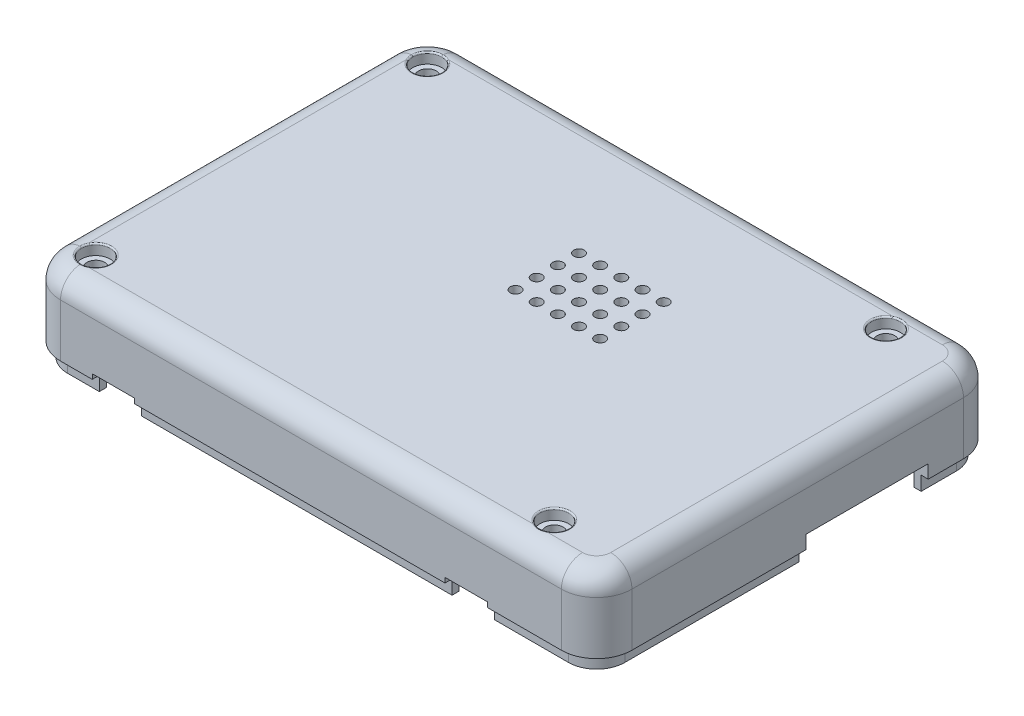
SolidWorks part; units mm, degrees
ref_plane "前视基准面" through (0, 0, 0) normal (0, 0, 1) x (1, 0, 0)
ref_plane "上视基准面" through (0, 0, 0) normal (0, 1, 0) x (1, 0, 0)
ref_plane "右视基准面" through (0, 0, 0) normal (1, 0, 0) x (0, 0, -1)
sketch "草图4" plane through (0, 0, 0) normal (0, 1, 0) x (1, 0, 0)
  line L1 (-118.546, 139.5567) -> (-41.546, 139.5567)
  line L2 (-118.546, 139.5567) -> (-118.546, 86.5567)
  line L3 (-118.546, 86.5567) -> (-41.546, 86.5567)
  line L4 (-41.546, 139.5567) -> (-41.546, 86.5567)
  line L5 (-39.546, 141.5567) -> (-39.546, 84.5567)
  line L6 (-120.546, 84.5567) -> (-39.546, 84.5567)
  line L7 (-120.546, 141.5567) -> (-120.546, 84.5567)
  line L8 (-120.546, 141.5567) -> (-39.546, 141.5567)
  circle A0 centre (-115.546, 136.5567) radius 1.25
  circle A1 centre (-50.546, 136.5567) radius 1.25
  circle A2 centre (-50.546, 89.5567) radius 1.25
  circle A3 centre (-115.546, 89.5567) radius 1.25
  circle A4 centre (-115.546, 136.5567) radius 2.5
  circle A5 centre (-50.546, 136.5567) radius 2.5
  circle A6 centre (-50.546, 89.5567) radius 2.5
  circle A7 centre (-115.546, 89.5567) radius 2.5
  dimension "D3" = 5
  dimension "D4" = 5
  dimension "D5" = 5
  dimension "D6" = 5
  dimension "D7" = 2.5
  dimension "D9" = 3
  dimension "D1" = 77
  dimension "D2" = 53
  dimension "D8" = 3
  dimension "D10" = 2
extrude "凸台-拉伸5" add sketch "草图4" against normal blind 3 contours A0 | A1 | A2 | A3 | L5 L6 L7 L8 region at (-115.546, 0, -136.5567) region at (-50.546, 0, -136.5567) region at (-50.546, 0, -89.5567) region at (-115.546, 0, -89.5567)
extrude "凸台-拉伸6" add sketch "草图4<4>" against normal blind 10.6 from surface contours A6 A2 | A7 A3 | A5 A1 | A4 A0 region at (-117.9753, 0, -136.5567) region at (-52.9753, 0, -136.5567) region at (-52.9753, 0, -89.5567) region at (-117.9753, 0, -89.5567) starting at face at (-115.546, -3, -88.3067)
sketch "草图4<4>" plane through (0, 0, 0) normal (0, 1, 0) x (1, 0, 0) same geometry as "草图4"
extrude "凸台-拉伸7" add sketch "草图4<5>" against normal blind 10.5 contours L8 L7 L6 L5 L1 L4 L3 L2 region at (-40.5364, 0, -113.0567)
sketch "草图4<5>" plane through (0, 0, 0) normal (0, 1, 0) x (1, 0, 0) same geometry as "草图4"
sketch "草图6" plane through (0, 0, -141.5567) normal (0, 0, -1) x (-1, 0, 0)
  line L0 (120.546, -10.5) -> (39.546, -10.5) construction
  line L1 (59.546, -10.5) -> (72.046, -10.5)
  line L2 (59.546, -8.35) -> (59.546, -12.65)
  line L3 (59.546, -12.65) -> (72.046, -12.65)
  line L4 (72.046, -8.35) -> (72.046, -12.65)
  line L5 (120.546, -10.5) -> (39.546, -10.5) construction
  line L6 (75.446, -10.5) -> (85.446, -10.5)
  line L7 (75.446, -8.35) -> (75.446, -12.65)
  line L8 (75.446, -12.65) -> (85.446, -12.65)
  line L9 (85.446, -8.35) -> (85.446, -12.65)
  line L10 (89.446, -10.5) -> (96.946, -10.5)
  line L11 (89.446, -7.35) -> (89.446, -13.65)
  line L12 (89.446, -13.65) -> (96.946, -13.65)
  line L13 (96.946, -7.35) -> (96.946, -13.65)
  line L14 (103.946, -10.5) -> (112.946, -10.5)
  line L15 (103.946, -10) -> (103.946, -10.5)
  line L16 (112.946, -10) -> (112.946, -10.5)
  line L18 (103.946, -10) -> (112.946, -10)
  line L19 (89.446, -7.35) -> (96.946, -7.35)
  line L20 (75.446, -8.35) -> (85.446, -8.35)
  line L21 (59.546, -8.35) -> (72.046, -8.35)
  line L23 (39.546, -10.5) -> (39.546, 0) construction
  line M25 (39.546, -10.5) -> (120.546, -10.5)
  dimension "D1" = 12.5
  dimension "D2" = 20
  dimension "D3" = 3.4
  dimension "D4" = 10
  dimension "D5" = 4
  dimension "D6" = 7.5
  dimension "D7" = 3.15
  dimension "D8" = 7
  dimension "D9" = 0.5
extrude "切除-拉伸1" cut sketch "草图6" against normal blind 2 contours L21 L2 L4 M25 | L20 L7 L9 M25 | L19 L11 L13 M25 | L18 L16 L14 L15 region at (-65.796, -9.425, -141.5567) region at (-93.196, -8.925, -141.5567) region at (-80.446, -9.425, -141.5567)
sketch "草图7" plane through (-120.546, 0, 0) normal (-1, 0, 0) x (0, 0, 1)
  line L1 (-133.2567, -10.5) -> (-133.2567, -3)
  line L2 (-133.2567, -3) -> (-124.3067, -3)
  line L3 (-124.3067, -3) -> (-124.3067, -10.5)
  line L4 (-141.5567, -10.5) -> (-141.5567, 0) construction
  line L6 (-84.5567, -10.5) -> (-84.5567, 0) construction
  line L11 (-106.4567, -9.3) -> (-95.5567, -9.3)
  line L12 (-106.4567, -9.3) -> (-106.4567, -10.5)
  line L13 (-141.5567, -10.5) -> (-84.5567, -10.5) construction
  line L18 (-95.5567, -9.3) -> (-95.5567, -10.5)
  line M23 (-141.5567, -10.5) -> (-84.5567, -10.5)
  dimension "D1" = 11
  dimension "D2" = 8.3
  dimension "D3" = 8.95
  dimension "D4" = 1.2
  dimension "D5" = 7.5
  dimension "D6" = 10.9
extrude "切除-拉伸2" cut sketch "草图7" against normal blind 2 contours L18 L11 L12 M23 | L3 L2 L1 M23 region at (-120.546, -9.9, -101.0067) region at (-120.546, -6.75, -128.7817)
sketch "草图8" plane through (0, 0, -84.5567) normal (0, 0, 1) x (1, 0, 0)
  line L0 (-120.546, -10.5) -> (-39.546, -10.5) construction
  line L1 (-111.046, -10.5) -> (-105.046, -10.5)
  line L2 (-111.046, -9.8) -> (-111.046, -11.2)
  line L3 (-111.046, -11.2) -> (-105.046, -11.2)
  line L4 (-105.046, -9.8) -> (-105.046, -11.2)
  line L5 (-39.546, -10.5) -> (-39.546, 0) construction
  line L6 (-61.046, -10.5) -> (-55.046, -10.5)
  line L7 (-61.046, -9.8) -> (-61.046, -11.2)
  line L8 (-61.046, -11.2) -> (-55.046, -11.2)
  line L9 (-55.046, -9.8) -> (-55.046, -11.2)
  line L10 (-120.546, -10.5) -> (-120.546, 0) construction
  line L11 (-120.546, -10.5) -> (-39.546, -10.5) construction
  line L12 (-61.046, -9.8) -> (-55.046, -9.8)
  line L13 (-111.046, -9.8) -> (-105.046, -9.8)
  line M18 (-120.546, -10.5) -> (-39.546, -10.5)
  dimension "D1" = 6
  dimension "D2" = 6
  dimension "D3" = 15.5
  dimension "D4" = 9.5
  dimension "D5" = 0.7
extrude "切除-拉伸3" cut sketch "草图8" against normal blind 2 contours L13 L2 L4 M18 | L12 L7 L9 M18 region at (-108.046, -10.15, -84.5567) region at (-58.046, -10.15, -84.5567)
sketch "草图9" plane through (-39.546, 0, 0) normal (1, 0, 0) x (0, 0, -1)
  line L0 (141.5567, -10.5) -> (84.5567, -10.5) construction
  line L1 (114.2567, -10.5) -> (131.5567, -10.5)
  line L2 (114.2567, -8.6) -> (114.2567, -12.4)
  line L3 (114.2567, -12.4) -> (131.5567, -12.4)
  line L4 (131.5567, -8.6) -> (131.5567, -12.4)
  line L5 (141.5567, -10.5) -> (141.5567, 0) construction
  line L6 (141.5567, -10.5) -> (84.5567, -10.5) construction
  line L7 (114.2567, -8.6) -> (131.5567, -8.6)
  line M12 (84.5567, -10.5) -> (141.5567, -10.5)
  dimension "D1" = 10
  dimension "D2" = 17.3
  dimension "D3" = 1.9
extrude "切除-拉伸4" cut sketch "草图9" against normal blind 2 contours L7 L2 L4 M12 region at (-39.546, -9.55, -122.9067)
fillet "圆角2" radius 3 4 edges at (-41.546, -6.75, -86.5567) (-41.546, -6.75, -139.5567) (-118.546, -6.75, -139.5567) (-118.546, -6.75, -86.5567)
fillet "圆角3" radius 5 4 edges at (-120.546, -5.25, -84.5567) (-39.546, -5.25, -84.5567) (-39.546, -5.25, -141.5567) (-120.546, -5.25, -141.5567)
fillet "圆角4" radius 3 8 edges at (-119.0815, 0, -86.0211) (-120.546, 0, -113.0567) (-119.0815, 0, -140.0922) (-80.046, 0, -141.5567) (-41.0104, 0, -140.0922) (-39.546, 0, -113.0567) (-41.0104, 0, -86.0211) (-80.046, 0, -84.5567)
fillet "圆角5" radius 2 2 edges at (-119.546, -9.3, -95.5567) (-119.546, -9.3, -106.4567)
fillet "圆角6" radius 3.5 2 edges at (-119.546, -3, -124.3067) (-119.546, -3, -133.2567)
sketch "草图10" plane through (0, 0, 0) normal (0, 1, 0) x (1, 0, 0)
  circle A0 centre (-50.546, 89.5567) radius 2.05
  circle A1 centre (-115.546, 89.5567) radius 2.05
  circle A2 centre (-115.546, 136.5567) radius 2.05
  circle A3 centre (-50.546, 136.5567) radius 2.05
  dimension "D1" = 4.1
extrude "切除-拉伸5" cut sketch "草图10" against normal blind 1.5
fillet "圆角7" radius 0.2 12 edges at (-116.9955, -0.0004, -88.1071) (-114.0964, 0, -135.1071) (-50.7834, -0.0002, -138.5929) (-50.3086, -0.0002, -87.5205) (-114.0964, 0, -91.0062) (-116.9955, -0.0004, -138.0062) (-50.546, 0, -134.5067) (-50.546, 0, -91.6067)
sketch "草图12" plane through (0, -10.5, 0) normal (0, -1, 0) x (1, 0, 0)
  line L0 (-59.546, -141.5567) -> (-44.546, -141.5567) construction
  line L1 (-44.546, -85.5567) -> (-115.546, -85.5567)
  line L2 (-40.546, -89.5567) -> (-40.546, -136.5567)
  line L3 (-44.546, -140.5567) -> (-115.546, -140.5567)
  line L4 (-119.546, -89.5567) -> (-119.546, -136.5567)
  line L5 (-39.546, -114.2567) -> (-39.546, -131.5567) construction
  line L6 (-105.046, -84.5567) -> (-61.046, -84.5567) construction
  line L7 (-120.546, -124.3067) -> (-120.546, -106.4567) construction
  line L8 (-44.546, -86.5567) -> (-115.546, -86.5567)
  line L9 (-118.546, -89.5567) -> (-118.546, -136.5567)
  line L10 (-44.546, -139.5567) -> (-115.546, -139.5567)
  line L11 (-41.546, -89.5567) -> (-41.546, -136.5567)
  line L12 (-55.046, -84.5567) -> (-55.046, -86.5567)
  line L13 (-55.046, -86.5567) -> (-55.046, -84.5567) construction
  line L14 (-61.046, -84.5567) -> (-61.046, -86.5567)
  line L15 (-61.046, -86.5567) -> (-61.046, -84.5567) construction
  line L16 (-40.546, -114.2567) -> (-41.546, -114.2567)
  line L17 (-41.546, -114.2567) -> (-39.546, -114.2567) construction
  line L18 (-41.546, -131.5567) -> (-40.546, -131.5567)
  line L19 (-59.546, -139.5567) -> (-59.546, -140.5567)
  line L20 (-59.546, -139.5567) -> (-59.546, -141.5567) construction
  line L21 (-72.046, -140.5567) -> (-72.046, -139.5567)
  line L22 (-72.046, -139.5567) -> (-72.046, -141.5567) construction
  line L23 (-75.446, -139.5567) -> (-75.446, -140.5567)
  line L24 (-75.446, -139.5567) -> (-75.446, -141.5567) construction
  line L25 (-96.946, -139.5567) -> (-96.946, -140.5567)
  line L26 (-96.946, -139.5567) -> (-96.946, -141.5567) construction
  line L27 (-103.946, -139.5567) -> (-103.946, -140.5567)
  line L28 (-103.946, -139.5567) -> (-103.946, -141.5567) construction
  line L29 (-112.946, -139.5567) -> (-112.946, -140.5567)
  line L30 (-112.946, -139.5567) -> (-112.946, -141.5567) construction
  line L31 (-85.446, -139.5567) -> (-85.446, -140.5567)
  line L32 (-89.446, -139.5567) -> (-89.446, -140.5567)
  line L33 (-89.446, -139.5567) -> (-89.446, -141.5567) construction
  line L34 (-118.546, -133.2567) -> (-120.546, -133.2567)
  line L35 (-118.546, -124.3067) -> (-120.546, -124.3067)
  line L36 (-118.546, -106.4567) -> (-120.546, -106.4567)
  line L37 (-118.546, -95.5567) -> (-120.546, -95.5567)
  line L38 (-105.046, -84.5567) -> (-105.046, -86.5567)
  line L39 (-111.046, -84.5567) -> (-111.046, -86.5567)
  arc A0 (-115.546, -140.5567) -> (-119.546, -136.5567) centre (-115.546, -136.5567) cw
  arc A1 (-115.546, -85.5567) -> (-119.546, -89.5567) centre (-115.546, -89.5567) ccw
  arc A2 (-44.546, -85.5567) -> (-40.546, -89.5567) centre (-44.546, -89.5567) cw
  arc A3 (-40.546, -136.5567) -> (-44.546, -140.5567) centre (-44.546, -136.5567) cw
  arc A4 (-115.546, -86.5567) -> (-118.546, -89.5567) centre (-115.546, -89.5567) ccw
  arc A5 (-115.546, -139.5567) -> (-118.546, -136.5567) centre (-115.546, -136.5567) cw
  arc A6 (-41.546, -136.5567) -> (-44.546, -139.5567) centre (-44.546, -136.5567) cw
  arc A7 (-44.546, -86.5567) -> (-41.546, -89.5567) centre (-44.546, -89.5567) cw
  line M5 (-72.046, -139.5567) -> (-75.446, -139.5567)
  line M6 (-75.446, -139.5567) -> (-75.446, -141.5567)
  line M8 (-72.046, -141.5567) -> (-72.046, -139.5567)
  dimension "D5" = 4
  dimension "D1" = 1
  dimension "D2" = 1
  dimension "D3" = 1
  dimension "D4" = 1
  dimension "D6" = 1
extrude "凸台-拉伸9" add sketch "草图12" along normal blind 2 contours L8 A7 L11 L16 L2 A2 L1 L12 | L11 A6 L10 L19 L3 A3 L2 L18 | L3 M8 M5 M6 | L10 L32 L3 L31 | L10 L27 L3 L25 | L10 A5 L9 L34 L4 A0 L3 L29 | L9 L36 L4 L35 | A4 L8 L39 L1 A1 L4 L37 L9 | L1 L38 L8 L14 region at (-41.9449, -10.5, -86.9556) region at (-83.046, -10.5, -86.0567) region at (-40.7562, -10.5, -134.0567) region at (-111.1772, -10.5, -86.0567) region at (-73.746, -10.5, -140.0567) region at (-119.046, -10.5, -115.3817) region at (-87.446, -10.5, -140.0567) region at (-119.046, -10.5, -133.3551) region at (-100.446, -10.5, -140.0567)
sketch "草图13" plane through (0, 0, 0) normal (0, 1, 0) x (1, 0, 0)
  line L1 (-44.546, 84.5567) -> (-115.546, 84.5567) construction
  line L2 (-39.546, 136.5567) -> (-39.546, 89.5567) construction
  line L4 (-67.546, 113.0567) -> (-83.546, 113.0567) construction
  line L5 (-67.546, 113.0567) -> (-67.546, 126.0567) construction
  line L6 (-67.546, 126.0567) -> (-83.546, 126.0567) construction
  line L7 (-83.546, 113.0567) -> (-83.546, 126.0567) construction
  circle A0 centre (-69.546, 115.0567) radius 0.75
  circle A1 centre (-72.546, 115.0567) radius 0.75
  circle A2 centre (-75.546, 115.0567) radius 0.75
  circle A3 centre (-78.546, 115.0567) radius 0.75
  circle A4 centre (-81.546, 115.0567) radius 0.75
  circle A5 centre (-72.546, 118.0567) radius 0.75
  circle A6 centre (-75.546, 118.0567) radius 0.75
  circle A7 centre (-78.546, 118.0567) radius 0.75
  circle A8 centre (-81.546, 118.0567) radius 0.75
  circle A9 centre (-72.546, 121.0567) radius 0.75
  circle A10 centre (-75.546, 121.0567) radius 0.75
  circle A11 centre (-78.546, 121.0567) radius 0.75
  circle A12 centre (-81.546, 121.0567) radius 0.75
  circle A13 centre (-72.546, 124.0567) radius 0.75
  circle A14 centre (-75.546, 124.0567) radius 0.75
  circle A15 centre (-78.546, 124.0567) radius 0.75
  circle A16 centre (-81.546, 124.0567) radius 0.75
  circle A17 centre (-69.546, 118.0567) radius 0.75
  circle A18 centre (-69.546, 121.0567) radius 0.75
  circle A19 centre (-69.546, 124.0567) radius 0.75
  dimension "D1" = 1.5
  dimension "D2" = 30
  dimension "D5" = 30.5
  dimension "D6" = 13
  dimension "D7" = 16
  dimension "D8" = 28
  dimension "D9" = 28.5
  dimension "D3" = 5
  dimension "D4" = 4
extrude "切除-拉伸6" cut sketch "草图13" against normal blind 3
